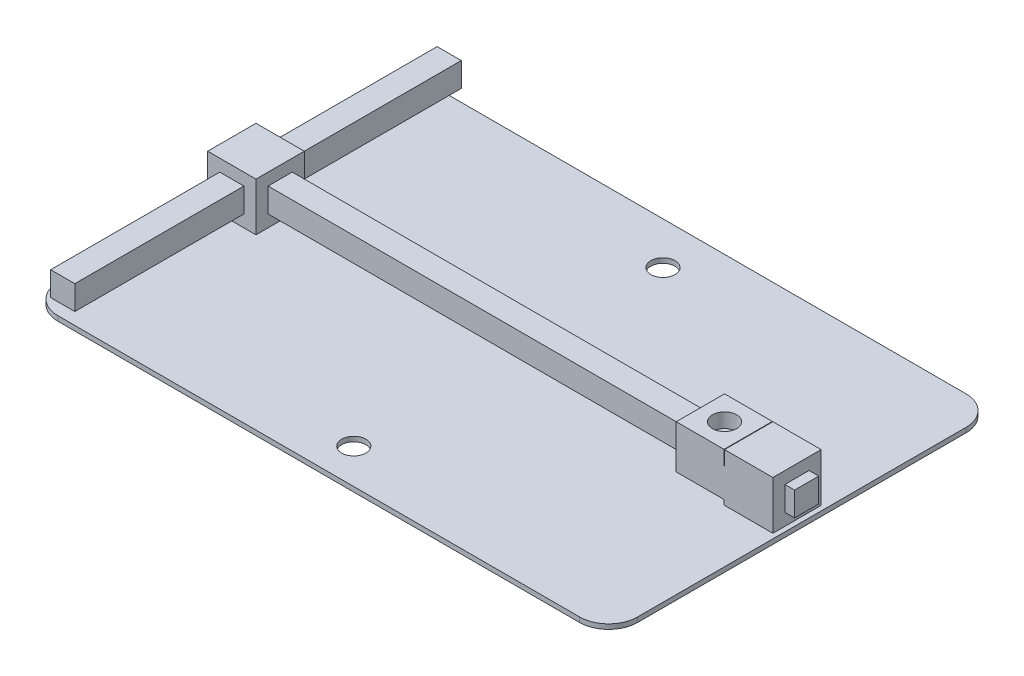
SolidWorks part; units mm, degrees
ref_plane "Front Plane" through (0, 0, 0) normal (0, 0, 1) x (1, 0, 0)
ref_plane "Top Plane" through (0, 0, 0) normal (0, 1, 0) x (1, 0, 0)
ref_plane "Right Plane" through (0, 0, 0) normal (1, 0, 0) x (0, 0, -1)
sketch "Sketch1" plane through (0, 0, 0) normal (0, 1, 0) x (1, 0, 0)
  line L1 (-54, -40) -> (54, -40)
  line L2 (-60, -34) -> (-60, 34)
  line L3 (-54, 40) -> (54, 40)
  line L4 (60, -34) -> (60, 34)
  line L5 (0, 40) -> (0, -40) construction
  line L6 (-60, 0) -> (60, 0) construction
  arc A0 (-60, -34) -> (-54, -40) centre (-54, -34) ccw
  arc A1 (54, -40) -> (60, -34) centre (54, -34) ccw
  arc A2 (60, 34) -> (54, 40) centre (54, 34) ccw
  arc A3 (-54, 40) -> (-60, 34) centre (-54, 34) ccw
  circle A4 centre (0, 31.25) radius 2.5
  circle A5 centre (0, -32.75) radius 2.5
  point P0 (0, 0)
  point P6 (-60, -40)
  point P12 (60, 40)
  point P15 (-60, 40)
  dimension "D3" = 6
  dimension "D4" = 5
  dimension "D6" = 5
  dimension "D1" = 80
  dimension "D2" = 120
  dimension "D5" = 8.75
  dimension "D7" = 7.25
extrude "Boss-Extrude1" add sketch "Sketch1" along normal blind 1
sketch "Sketch2" plane through (0, 0, 0) normal (0, -1, 0) x (1, 0, 0)
  line L0 (0, 0) -> (-60, 0) construction
  line L1 (-60, 0) -> (60, 0) construction
  line L4 (-60, 34) -> (-60, -34)
  line L5 (-54, -40) -> (54, -40)
  line L6 (60, -34) -> (60, 34)
  line L7 (54, 40) -> (-54, 40)
  line L8 (-60, 34) -> (-60, -34)
  line L9 (-54, -40) -> (54, -40)
  line L10 (60, -34) -> (60, 34)
  line L11 (54, 40) -> (-54, 40)
  circle A0 centre (-54, 34) radius 3.5
  circle A1 centre (54, 34) radius 3.5
  circle A2 centre (54, -34) radius 3.5
  circle A3 centre (-54, -34) radius 3.5
  arc A4 (-54, 40) -> (-60, 34) centre (-54, 34) ccw
  arc A5 (-60, -34) -> (-54, -40) centre (-54, -34) ccw
  arc A6 (54, -40) -> (60, -34) centre (54, -34) ccw
  arc A7 (60, 34) -> (54, 40) centre (54, 34) ccw
  arc A8 (-54, 40) -> (-60, 34) centre (-54, 34) ccw
  arc A9 (-60, -34) -> (-54, -40) centre (-54, -34) ccw
  arc A10 (54, -40) -> (60, -34) centre (54, -34) ccw
  arc A11 (60, 34) -> (54, 40) centre (54, 34) ccw
  circle A12 centre (-54, 0) radius 3
  circle A13 centre (54, 0) radius 3
  dimension "D2" = 7
  dimension "D3" = 7
  dimension "D4" = 7
  dimension "D5" = 7
  dimension "D6" = 6
  dimension "D7" = 6
  dimension "D1" = 0
extrude "Boss-Extrude2" add sketch "Sketch2" along normal blind 1.5 contours A0 | A12 | A3 | A1 | A2 | A13 region at (-54, 0, 34) region at (54, 0, 34) region at (-54, 0, -34) region at (-54, 0, 0)
sketch "Sketch3" plane through (0, 1, 0) normal (0, 1, 0) x (1, 0, 0)
  line L0 (54, 40) -> (54, -40) construction
  line L1 (54, 40) -> (-54, 40) construction
  line L2 (-54, -40) -> (54, -40) construction
  line L3 (60, -34) -> (60, 34) construction
  line L4 (59, -5) -> (49, -5)
  line L5 (59, -5) -> (59, 5)
  line L6 (59, 5) -> (49, 5)
  line L7 (49, -5) -> (49, 5)
  line L8 (54, 5) -> (54, -5) construction
  line L9 (59, 0) -> (49, 0) construction
  line L10 (-53, 40) -> (-53, -40) construction
  line L11 (-60, 34) -> (-60, -34) construction
  line L12 (-48, -5) -> (-58, -5)
  line L13 (-48, -5) -> (-48, 5)
  line L14 (-48, 5) -> (-58, 5)
  line L15 (-58, -5) -> (-58, 5)
  line L16 (-53, 5) -> (-53, -5) construction
  line L17 (-48, 0) -> (-58, 0) construction
  line L19 (39, -5) -> (49, -5)
  line L20 (39, -5) -> (39, 5)
  line L21 (39, 5) -> (49, 5)
  line L22 (49, -5) -> (49, 5)
  line L23 (44, 5) -> (44, -5) construction
  line L24 (39, 0) -> (49, 0) construction
  point P6 (54, 0)
  point P14 (-53, 0)
  point P20 (44, 0)
  dimension "D1" = 10
  dimension "D2" = 10
  dimension "D3" = 6
  dimension "D4" = 10
  dimension "D5" = 10
  dimension "D6" = 7
  dimension "D7" = 10
extrude "Boss-Extrude3" add sketch "Sketch3" along normal blind 10 contours L7 L4 L5 L6 | L21 L20 L19 L7 | L15 L12 L13 L14 region at (54, 1, 0) region at (44, 1, 0) region at (-53, 1, 0)
sketch "Sketch4" plane through (0, 0, 5) normal (0, 0, 1) x (1, 0, 0)
  line L0 (-53, 11) -> (-53, 1) construction
  line L2 (-50.5, 3.5) -> (-55.5, 3.5)
  line L3 (-50.5, 3.5) -> (-50.5, 8.5)
  line L4 (-58, 1) -> (-48, 1)
  line L5 (-48, 1) -> (-48, 11)
  line L6 (-48, 11) -> (-58, 11)
  line L7 (-58, 11) -> (-58, 1)
  line L8 (-58, 1) -> (-48, 1)
  line L9 (-48, 1) -> (-48, 11)
  line L11 (-58, 11) -> (-58, 1)
  line L12 (-50.5, 8.5) -> (-55.5, 8.5)
  line L13 (-55.5, 3.5) -> (-55.5, 8.5)
  line L14 (-53, 8.5) -> (-53, 3.5) construction
  line L15 (-50.5, 6) -> (-55.5, 6) construction
  line L19 (-48, 11) -> (-58, 11)
  point P6 (-53, 6)
  dimension "D2" = 5
  dimension "D3" = 5
  dimension "D4" = 5
  dimension "D1" = 0
sketch "Sketch5" plane through (59, 0, 0) normal (1, 0, 0) x (0, 0, -1)
  line L0 (0, 11) -> (0, 1) construction
  line L2 (2.5, 3.5) -> (-2.5, 3.5)
  line L3 (2.5, 3.5) -> (2.5, 8.5)
  line L4 (-5, 1) -> (5, 1)
  line L5 (5, 1) -> (5, 11)
  line L6 (5, 11) -> (-5, 11)
  line L7 (-5, 11) -> (-5, 1)
  line L8 (-5, 1) -> (5, 1)
  line L9 (5, 1) -> (5, 11)
  line L11 (-5, 11) -> (-5, 1)
  line L12 (2.5, 8.5) -> (-2.5, 8.5)
  line L13 (-2.5, 3.5) -> (-2.5, 8.5)
  line L14 (0, 8.5) -> (0, 3.5) construction
  line L15 (2.5, 6) -> (-2.5, 6) construction
  line L19 (5, 11) -> (-5, 11)
  point P6 (0, 6)
  dimension "D2" = 5
  dimension "D3" = 5
  dimension "D1" = 0
extrude "Boss-Extrude4" add sketch "Sketch4" along normal blind 35 and the other way blind 45 contours L13 L2 L3 L12 region at (-53, 6, 5)
extrude "Boss-Extrude5" add sketch "Sketch5" along normal blind 2 and the other way blind 110 contours L3 L12 L13 L2
sketch "Sketch6" plane through (0, 11, 0) normal (0, 1, 0) x (1, 0, 0)
  line L0 (48.95, 5) -> (48.95, -5) construction
  line L2 (48.9, -5) -> (49, -5)
  line L3 (48.9, -5) -> (48.9, 5)
  line L4 (59, 5) -> (39, 5)
  line L5 (39, 5) -> (39, -5)
  line L6 (39, -5) -> (59, -5)
  line L7 (59, -5) -> (59, 5)
  line L8 (59, 5) -> (39, 5)
  line L9 (39, 5) -> (39, -5)
  line L10 (39, -5) -> (59, -5)
  line L11 (59, -5) -> (59, 5)
  line L12 (48.9, 5) -> (49, 5)
  line L13 (49, -5) -> (49, 5)
  line L14 (48.95, 5) -> (48.95, -5) construction
  line L15 (48.9, 0) -> (49, 0) construction
  circle A0 centre (44, 0) radius 2.5
  point P6 (48.95, 0)
  line M7 (59, 5) -> (39, 5)
  line M8 (39, 5) -> (39, -5)
  line M9 (39, -5) -> (59, -5)
  dimension "D3" = 5
  dimension "D2" = 0.1
  dimension "D4" = 5
  dimension "D1" = 0
extrude "Cut-Extrude4" cut sketch "Sketch6" along normal blind 1 from surface contours L3 A0 M9 M7 M8 | A0 region at (43.95, 11, 4.8593) region at (44, 11, 0) starting at face at (-53, 1, 0)
extrude "Cut-Extrude5" cut sketch "Sketch6<3>" against normal blind 3 contours A0 | L3 L12 L13 L2 region at (44, 11, 0)
sketch "Sketch6<3>" plane through (0, 11, 0) normal (0, 1, 0) x (1, 0, 0) same geometry as "Sketch6"
